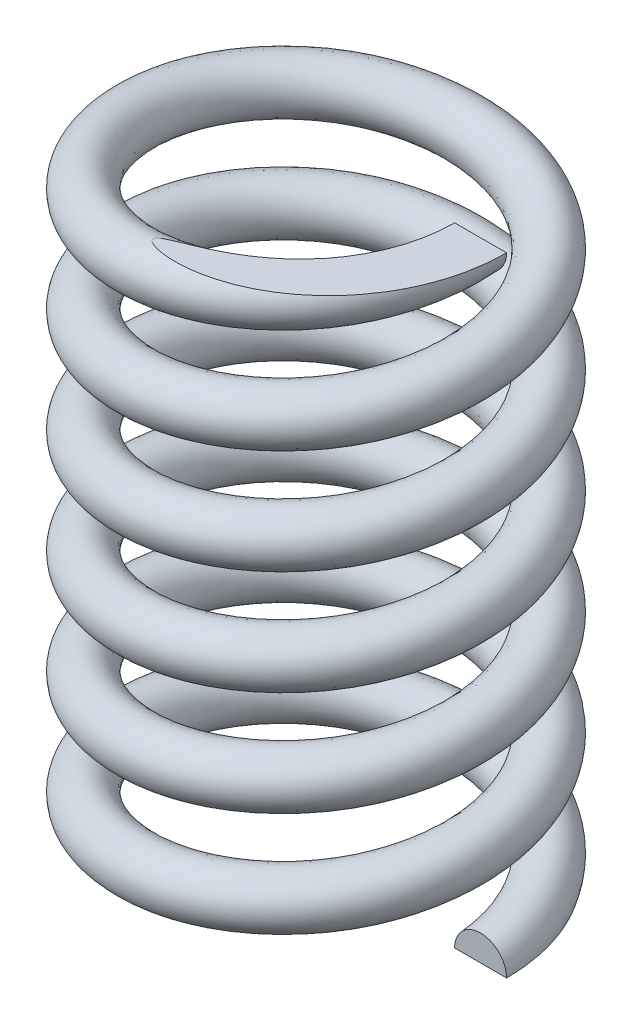
SolidWorks part; units mm, degrees
material "Chrome Stainless Steel"
ref_plane "Спереди" through (0, 0, 0) normal (0, 0, 1) x (1, 0, 0)
ref_plane "Сверху" through (0, 0, 0) normal (0, 1, 0) x (1, 0, 0)
ref_plane "Справа" through (0, 0, 0) normal (1, 0, 0) x (0, 0, -1)
sketch "Эскиз1" plane through (0, 0, 0) normal (0, 1, 0) x (1, 0, 0)
  circle A0 centre (0, 0) radius 1.9
  dimension "D1" = 3.8
curve "Спираль1" pitch 1.2083 height 7.25 radius 1.9 centre (0, 0, 0) axis (0, 1, 0) start towards (1, 0, 0)
sketch "Эскиз2" plane through (0, 0, 0) normal (0, 0, 1) x (1, 0, 0)
  circle A0 centre (1.9, 0) radius 0.3
  spline S0 degree 3 poles (1.9, 0) (1.9, 0.025) (1.8011, 0.0756) (1.3785, 0.151) (0.746, 0.2266) (0, 0.3021) (-0.746, 0.3776) (-1.3785, 0.4531) (-1.8011, 0.5286) (-1.9495, 0.6042) (-1.8011, 0.6797) (-1.3785, 0.7552) (-0.746, 0.8307) (0, 0.9062) (0.746, 0.9818) (1.3785, 1.0573) (1.8011, 1.1328) (1.9495, 1.2083) (1.8011, 1.2839) (1.3785, 1.3594) (0.746, 1.4349) (0, 1.5104) (-0.746, 1.5859) (-1.3785, 1.6615) (-1.8011, 1.737) (-1.9495, 1.8125) (-1.8011, 1.888) (-1.3785, 1.9635) (-0.746, 2.0391) (0, 2.1146) (0.746, 2.1901) (1.3785, 2.2656) (1.8011, 2.3411) (1.9495, 2.4167) (1.8011, 2.4922) (1.3785, 2.5677) (0.746, 2.6432) (0, 2.7187) (-0.746, 2.7943) (-1.3785, 2.8698) (-1.8011, 2.9453) (-1.9495, 3.0208) (-1.8011, 3.0964) (-1.3785, 3.1719) (-0.746, 3.2474) (0, 3.3229) (0.746, 3.3984) (1.3785, 3.474) (1.8011, 3.5495) (1.9495, 3.625) (1.8011, 3.7005) (1.3785, 3.776) (0.746, 3.8516) (0, 3.9271) (-0.746, 4.0026) (-1.3785, 4.0781) (-1.8011, 4.1536) (-1.9495, 4.2292) (-1.8011, 4.3047) (-1.3785, 4.3802) (-0.746, 4.4557) (0, 4.5313) (0.746, 4.6068) (1.3785, 4.6823) (1.8011, 4.7578) (1.9495, 4.8333) (1.8011, 4.9089) (1.3785, 4.9844) (0.746, 5.0599) (0, 5.1354) (-0.746, 5.2109) (-1.3785, 5.2865) (-1.8011, 5.362) (-1.9495, 5.4375) (-1.8011, 5.513) (-1.3785, 5.5885) (-0.746, 5.6641) (0, 5.7396) (0.746, 5.8151) (1.3785, 5.8906) (1.8011, 5.9661) (1.9495, 6.0417) (1.8011, 6.1172) (1.3785, 6.1927) (0.746, 6.2682) (0, 6.3438) (-0.746, 6.4193) (-1.3785, 6.4948) (-1.8011, 6.5703) (-1.9495, 6.6458) (-1.8011, 6.7214) (-1.3785, 6.7969) (-0.746, 6.8724) (0, 6.9479) (0.746, 7.0234) (1.3785, 7.099) (1.8011, 7.1744) (1.9, 7.225) (1.9, 7.25) knots 0 0 0 0 0.010417 0.020833 0.03125 0.041667 0.052083 0.0625 0.072917 0.083333 0.09375 0.104167 0.114583 0.125 0.135417 0.145833 0.15625 0.166667 0.177083 0.1875 0.197917 0.208333 0.21875 0.229167 0.239583 0.25 0.260417 0.270833 0.28125 0.291667 0.302083 0.3125 0.322917 0.333333 0.34375 0.354167 0.364583 0.375 0.385417 0.395833 0.40625 0.416667 0.427083 0.4375 0.447917 0.458333 0.46875 0.479167 0.489583 0.5 0.510417 0.520833 0.53125 0.541667 0.552083 0.5625 0.572917 0.583333 0.59375 0.604167 0.614583 0.625 0.635417 0.645833 0.65625 0.666667 0.677083 0.6875 0.697917 0.708333 0.71875 0.729167 0.739583 0.75 0.760417 0.770833 0.78125 0.791667 0.802083 0.8125 0.822917 0.833333 0.84375 0.854167 0.864583 0.875 0.885417 0.895833 0.90625 0.916667 0.927083 0.9375 0.947917 0.958333 0.96875 0.979167 0.989583 1 1 1 1 construction
  dimension "D1" = 0.6
sweep "По траектории1" add profiles "Эскиз2" path "Спираль1"
ref_point "Точка1"
ref_plane "Плоскость1" through (0, 7.25, 0) normal (0, 1, 0) x (1, 0, 0)
sketch "Эскиз3" plane through (0, 0, 0) normal (0, 0, 1) x (1, 0, 0)
  line L0 (50, 7.25) -> (-50, 7.25) construction
  line L1 (-17.2005, 7.25) -> (17.2005, 7.25)
  line L2 (-17.2005, 7.25) -> (-17.2005, 0)
  line L3 (-17.2005, 0) -> (17.2005, 0)
  line L4 (17.2005, 7.25) -> (17.2005, 0)
  line L5 (-17.2005, 7.25) -> (17.2005, 0) construction
  line L6 (-17.2005, 0) -> (17.2005, 7.25) construction
  point P0 (0, 3.625)
extrude "Вырез-Вытянуть1" cut sketch "Эскиз3" against normal through all both and the other way through all flip side to cut
ref_axis "Ось1" through (0, 50, 0) along (0, -1, 0)
